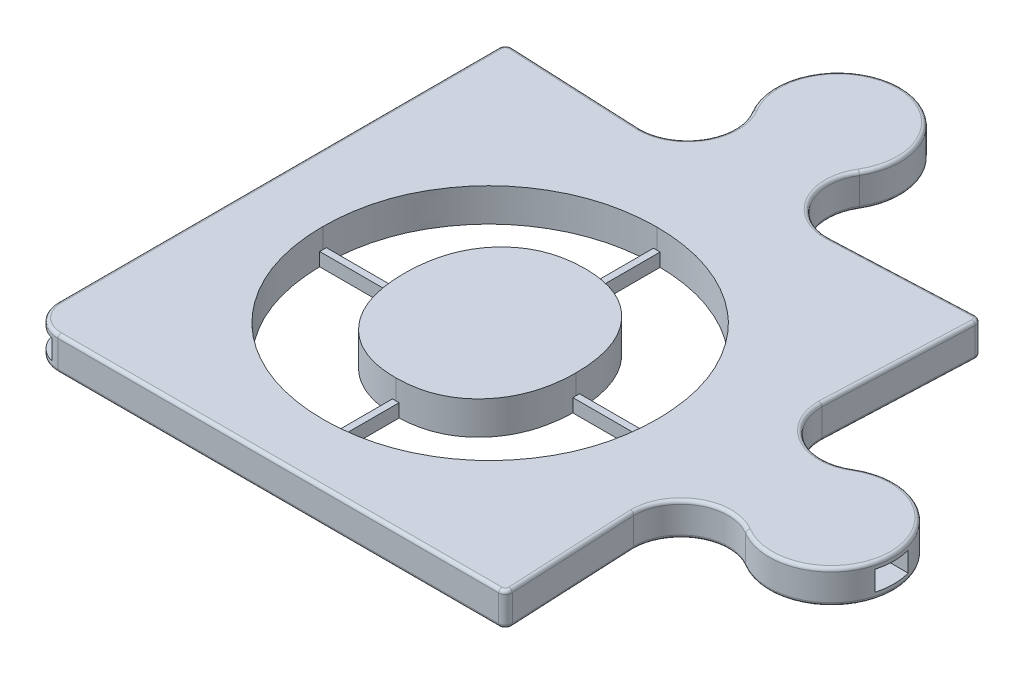
SolidWorks part; units mm, degrees
ref_plane "Front Plane" through (0, 0, 0) normal (0, 0, 1) x (1, 0, 0)
ref_plane "Top Plane" through (0, 0, 0) normal (0, 1, 0) x (1, 0, 0)
ref_plane "Right Plane" through (0, 0, 0) normal (1, 0, 0) x (0, 0, -1)
sketch "Sketch1" plane through (0, 0, 0) normal (0, 1, 0) x (1, 0, 0)
  line L0 (-31, -36) -> (37, -36) construction
  line L1 (-36, 37) -> (-36, -31) construction
  line L2 (-14.1421, 36) -> (-36, 37) construction
  line L3 (37, 37) -> (14.1421, 36) construction
  line L4 (36, 13.1421) -> (37, 37) construction
  line L5 (37, -36) -> (36, -15.1421) construction
  line L6 (-35.4, 36.3719) -> (-35.4, -31)
  line L7 (-36, 36) -> (36, 36) construction
  line L8 (-36, 36) -> (-36, -36) construction
  line L9 (-36, -36) -> (36, -36) construction
  line L10 (36, 36) -> (36, -36) construction
  line L11 (-31, -35.4) -> (36.3705, -35.4)
  line L12 (36.3705, -35.4) -> (35.4, -15.1568)
  line L13 (35.4, 13.155) -> (36.3732, 36.372)
  line L14 (36.3732, 36.372) -> (14.1555, 35.4)
  line L15 (-14.1562, 35.4) -> (-35.4, 36.3719)
  line L16 (-30, -24) -> (30, -24) construction
  line L17 (-30, 29) -> (30, 29) construction
  line L18 (-30, 29) -> (-30, -31) construction
  line L19 (-30, -31) -> (30, -31) construction
  line L20 (30, 29) -> (30, -31) construction
  line L21 (-30, 24) -> (30, 24) construction
  line L22 (-30, 24) -> (-30, -26) construction
  line L23 (-30, -26) -> (30, -26) construction
  line L24 (30, 24) -> (30, -26) construction
  arc A0 (-36, -31) -> (-31, -36) centre (-31, -31) ccw construction
  arc A1 (-14.1421, 36) -> (-8.571, 45.8485) centre (-14.1421, 42.5) ccw construction
  arc A2 (8.571, 45.8485) -> (-8.571, 45.8485) centre (0, 51) ccw construction
  arc A3 (8.571, 45.8485) -> (14.1421, 36) centre (14.1421, 42.5) ccw construction
  arc A4 (36, 13.1421) -> (45.8485, 7.571) centre (42.5, 13.1421) ccw construction
  arc A5 (45.8485, -9.571) -> (45.8485, 7.571) centre (51, -1) ccw construction
  arc A6 (45.8485, -9.571) -> (36, -15.1421) centre (42.5, -15.1421) ccw construction
  arc A7 (-35.4, -31) -> (-31, -35.4) centre (-31, -31) ccw
  arc A8 (46.1576, -9.0567) -> (35.4, -15.1568) centre (42.5, -15.1421) ccw
  arc A9 (46.1576, -9.0567) -> (46.1576, 7.0567) centre (51, -1) ccw
  arc A10 (35.4, 13.155) -> (46.1576, 7.0567) centre (42.5, 13.1421) ccw
  arc A11 (8.0567, 46.1576) -> (14.1555, 35.4) centre (14.1421, 42.5) ccw
  arc A12 (8.0567, 46.1576) -> (-8.0567, 46.1576) centre (0, 51) ccw
  arc A13 (-14.1562, 35.4) -> (-8.0567, 46.1576) centre (-14.1421, 42.5) ccw
  point P32 (36, 0)
  point P34 (0, 36)
  dimension "D5" = 6.5
  dimension "D6" = 10
  dimension "D7" = 6.5
  dimension "D13" = 5
  dimension "D9" = 10
  dimension "D11" = 6.5
  dimension "D12" = 6.5
  dimension "D1" = 72
  dimension "D2" = 1
  dimension "D3" = 1
  dimension "D4" = 15
  dimension "D8" = 1
  dimension "D10" = 35
  dimension "D14" = 15
  dimension "D15" = 36
  dimension "D16" = 1
  dimension "D18" = 60
  dimension "D19" = 60
  dimension "D20" = 5
  dimension "D21" = 6
  dimension "D22" = 5
  dimension "D23" = 50
  dimension "D24" = 2
  dimension "D17" = 0.6
extrude "Boss-Extrude1" add sketch "Sketch1" along normal blind 5
sketch "Sketch6" plane through (0, 0, 0) normal (0, -1, 0) x (1, 0, 0)
  line L0 (-35.4, -36.3719) -> (-35.4, 31) construction
  line L1 (-35.4, 17.9) -> (-27.4, 17.9)
  line L2 (-35.4, 17.9) -> (-35.4, -16.1)
  line L3 (-35.4, -16.1) -> (-27.4, -16.1)
  line L4 (-27.4, 17.9) -> (-27.4, -16.1)
  line L5 (-31, 35.4) -> (36.3705, 35.4) construction
  line L6 (-35.4, 14.65) -> (-30.4, 14.65)
  line L7 (-35.4, 14.65) -> (-35.4, -12.85)
  line L8 (-35.4, -12.85) -> (-30.4, -12.85)
  line L9 (-30.4, 14.65) -> (-30.4, -12.85)
  point P15 (-27.4, 0.9)
  point P16 (-30.4, 0.9)
  line M28 (-35.4, 31) -> (-35.4, -36.3719)
  dimension "D1" = 8
  dimension "D2" = 20.75
  dimension "D3" = 27.5
  dimension "D4" = 5
  dimension "D5" = 34
extrude "Cut-Extrude3" cut sketch "Sketch6" against normal blind 3 from offset 1 contours L6 L9 L8 L3 L4 L1 M28 | L9 L6 L2 L8 region at (-29.8665, 0, 0.9) region at (-32.9, 0, 0.9) offset against normal yes
extrude "Cut-Extrude4" cut sketch "Sketch6<3>" against normal up to next contours L9 L6 L2 L8 region at (-32.9, 0, 0.9)
sketch "Sketch6<3>" plane through (0, 0, 0) normal (0, -1, 0) x (1, 0, 0) same geometry as "Sketch6"
sketch "Sketch8" plane through (0, 0, 0) normal (0, -1, 0) x (1, 0, 0)
  line L1 (-2.5, -51.4) -> (2.5, -51.4)
  line L2 (-2.5, -51.4) -> (-2.5, -60.4)
  line L3 (-2.5, -60.4) -> (2.5, -60.4)
  line L4 (2.5, -51.4) -> (2.5, -60.4)
  line L5 (51.4, 3.5) -> (60.4, 3.5)
  line L6 (51.4, 3.5) -> (51.4, -1.5)
  line L7 (51.4, -1.5) -> (60.4, -1.5)
  line L8 (60.4, 3.5) -> (60.4, -1.5)
  arc A0 (-8.0567, -46.1576) -> (8.0567, -46.1576) centre (0, -51) ccw construction
  arc A1 (46.1576, -7.0567) -> (46.1576, 9.0567) centre (51, 1) ccw construction
  point P4 (0, -60.4)
  point P13 (60.4, 1)
  dimension "D1" = 5
  dimension "D2" = 9
  dimension "D3" = 5
  dimension "D4" = 9
extrude "Cut-Extrude5" cut sketch "Sketch8" against normal blind 3 from offset 1 offset against normal yes
sketch "Sketch9" plane through (0, 0, 0) normal (0, -1, 0) x (1, 0, 0)
  line L0 (-31, 35.4) -> (36.3705, 35.4) construction
  line L1 (-35.4, 14.65) -> (-35.4, 31) construction
  line L2 (-31.7636, 35.3332) -> (-35.4, 31) construction
  line L3 (-33.2571, 29.735) -> (-30.0429, 33.565) construction
  line L4 (-30.0429, 33.565) -> (-33.2571, 29.735) construction
  line L5 (-30.0429, 33.565) -> (-32.7119, 35.8048)
  line L6 (-33.2571, 29.735) -> (-35.926, 31.9747)
  line L7 (-32.7119, 35.8048) -> (-35.926, 31.9747)
  circle A0 centre (-31.65, 31.65) radius 2.5
  arc A1 (-31, 35.4) -> (-35.4, 31) centre (-31, 31) ccw construction
  arc M41 (-31, 35.4) -> (-35.4, 31) centre (-31, 31) ccw
  dimension "D1" = 5
  dimension "D3" = 3.75
  dimension "D4" = 5.6569
  dimension "D2" = 3.75
extrude "Cut-Extrude6" cut sketch "Sketch9" against normal blind 3 from offset 1 contours A0 L5 L6 M41 | A0 L5 region at (-33.6239, 0, 33.3064) region at (-31.65, 0, 31.65) offset against normal yes
sketch "Sketch11" plane through (-35.4, 0, 0) normal (-1, 0, 0) x (0, 0, 1)
  line L0 (-13.155, 0) -> (-36.372, 0) construction
  line L1 (-25.1, 3) -> (-19.1, 3)
  line L2 (-25.1, 3) -> (-25.1, 1.5)
  line L3 (-25.1, 1.5) -> (-19.1, 1.5)
  line L4 (-19.1, 3) -> (-19.1, 1.5)
  line L5 (-16.1, 4) -> (-16.1, 1) construction
  line L6 (35.4, 0) -> (15.1568, 0) construction
  line L7 (20.9, 3) -> (26.9, 3)
  line L8 (20.9, 3) -> (20.9, 1.5)
  line L9 (20.9, 1.5) -> (26.9, 1.5)
  line L10 (26.9, 3) -> (26.9, 1.5)
  line L12 (17.9, 4) -> (17.9, 1) construction
  dimension "D1" = 3
  dimension "D2" = 1.5
  dimension "D3" = 3
  dimension "D4" = 6
  dimension "D5" = 3
  dimension "D6" = 1.5
  dimension "D7" = 6
  dimension "D8" = 3
fillet "Fillet1" radius 0.5 17 edges at (-35.4, 0, 22.825) (-34.1113, 0, 34.1113) (2.6853, 0, 35.4) (35.8853, 0, 25.2784) (38.9978, 0, 8.966) (60.4, 0, 1) (38.9986, 0, -6.9655) (35.8866, 0, -24.7635) (25.2643, 0, -35.886) (7.9657, 0, -38.9984) (0, 0, -60.4) (-7.9658, 0, -38.9981) (-24.7781, 0, -35.886) (-35.4, 0, -24.611) (-32.9, 0, -12.85) (-30.4, 0, 0.9) (-32.9, 0, 14.65)
fillet "Fillet2" radius 0.5 13 edges at (-7.9658, 5, -38.9981) (0, 5, -60.4) (7.9657, 5, -38.9984) (25.2643, 5, -35.886) (35.8866, 5, -24.7635) (38.9986, 5, -6.9655) (60.4, 5, 1) (38.9978, 5, 8.966) (35.8853, 5, 25.2784) (2.6853, 5, 35.4) (-34.1113, 5, 34.1113) (-35.4, 5, -2.686) (-24.7781, 5, -35.886)
fillet "Fillet3" radius 1 9 edges at (36.2202, 0.1464, -36.2187) (36.2202, 4.8536, -36.2187) (36.3732, 2.5, -36.372) (-35.2536, 0.1464, -36.2186) (-35.2536, 4.8536, -36.2186) (36.2169, 0.1464, 35.2536) (36.2169, 4.8536, 35.2536) (36.3705, 2.5, 35.4) (-35.4, 2.5, -36.3719)
extrude "Cut-Extrude9" cut sketch "Sketch11" against normal blind 3
chamfer "Chamfer1" distance 1 angle 50 2 edges at (-35.4, 1.5, 23.9) (-35.4, 1.5, -22.1) first distance on face at (-35.4, 2.25, -22.1)
sketch "Sketch12" plane through (0, 5, 0) normal (0, 1, 0) x (1, 0, 0)
  text T0 "O" font "Poppins" height 49
extrude "Cut-Extrude10" cut sketch "Sketch12" against normal through all
sketch "Sketch13" plane through (0, 5, 0) normal (0, 1, 0) x (1, 0, 0)
  line L0 (0, 24) -> (0.0303, -26.4847) construction
  line L1 (-30, 24) -> (30, 24) construction
  line L2 (-25.1665, -1.3586) -> (25.0958, -1.3586) construction
  line L4 (-25.1589, -0.8614) -> (-12.9392, -0.8614)
  line L5 (-25.1589, -0.8614) -> (-25.1589, -1.8614)
  line L6 (-25.1589, -1.8614) -> (-12.9392, -1.8614)
  line L7 (-12.9392, -0.8614) -> (-12.9392, -1.8614)
  line L8 (-0.4686, 12.8686) -> (0.5314, 12.8686)
  line L9 (-0.4686, 12.8686) -> (-0.4686, 23.6878)
  line L10 (-0.4686, 23.6878) -> (0.5314, 23.6878)
  line L11 (0.5314, 12.8686) -> (0.5314, 23.6878)
  line L12 (0.5303, -15.5856) -> (-0.4697, -15.5856)
  line L13 (0.5303, -15.5856) -> (0.5303, -26.4758)
  line L14 (0.5303, -26.4758) -> (-0.4697, -26.4758)
  line L15 (-0.4697, -15.5856) -> (-0.4697, -26.4758)
  line L16 (12.9391, -1.8523) -> (25.0882, -1.8523)
  line L17 (12.9391, -1.8523) -> (12.9391, -0.8523)
  line L18 (12.9391, -0.8523) -> (25.0882, -0.8523)
  line L19 (25.0882, -1.8523) -> (25.0882, -0.8523)
  spline S0 degree 3 poles (-25.1665, -1.3586) (-25.158, -0.7657) (-25.1413, 0.4055) (-24.9715, 2.1354) (-24.7121, 3.8229) (-24.3394, 5.4626) (-23.8605, 7.0572) (-23.2882, 8.6058) (-22.5965, 10.1065) (-21.7999, 11.5554) (-20.9138, 12.9437) (-19.9533, 14.2599) (-18.9184, 15.4988) (-17.8112, 16.6553) (-16.6304, 17.7394) (-15.366, 18.7289) (-14.0455, 19.6707) (-12.6382, 20.4966) (-11.1928, 21.2616) (-9.6889, 21.9035) (-8.1562, 22.4608) (-6.5888, 22.9194) (-4.9838, 23.2583) (-3.3459, 23.5132) (-1.6693, 23.668) (-0.5389, 23.6872) (0.0303, 23.6968) knots 0 0 0 0 0.04484 0.08858 0.131371 0.173938 0.215675 0.257256 0.298736 0.340565 0.382247 0.423253 0.463751 0.50428 0.544298 0.584907 0.625674 0.666905 0.708254 0.749318 0.790485 0.831589 0.872748 0.914494 0.956941 1 1 1 1 construction
  spline S1 degree 3 poles (-12.9468, -1.3586) (-12.9398, -1.8877) (-12.9261, -2.9186) (-12.7421, -4.4232) (-12.4797, -5.8477) (-12.0907, -7.1924) (-11.6004, -8.4567) (-10.9892, -9.6372) (-10.2689, -10.7342) (-9.4419, -11.7421) (-8.5249, -12.6492) (-7.5321, -13.4479) (-6.4478, -14.1052) (-5.2974, -14.6507) (-4.0725, -15.08) (-2.7722, -15.3798) (-1.3956, -15.5652) (-0.4517, -15.587) (0.0303, -15.5981) knots 0 0 0 0 0.072957 0.142149 0.208827 0.272625 0.334984 0.395642 0.455672 0.515736 0.575181 0.633355 0.691107 0.749695 0.808745 0.869807 0.933524 1 1 1 1 construction
  spline S2 degree 3 poles (0.0303, 12.8809) (-0.4518, 12.8701) (-1.3959, 12.849) (-2.7705, 12.6588) (-4.0746, 12.3771) (-5.2939, 11.9393) (-6.4542, 11.4131) (-7.5255, 10.7376) (-8.5257, 9.9541) (-9.4411, 9.0548) (-10.2718, 8.0564) (-10.9892, 6.9601) (-11.5978, 5.7823) (-12.0949, 4.5203) (-12.4789, 3.1705) (-12.7432, 1.733) (-12.9254, 0.2147) (-12.9396, -0.8262) (-12.9468, -1.3586) knots 0 0 0 0 0.066421 0.130085 0.190992 0.249994 0.308336 0.366284 0.424122 0.483193 0.542849 0.60283 0.663437 0.725312 0.789504 0.856583 0.92664 1 1 1 1 construction
  spline S3 degree 3 poles (0.0303, 23.6968) (0.5995, 23.6872) (1.7299, 23.6681) (3.4097, 23.5123) (5.0513, 23.2594) (6.6595, 22.9193) (8.2269, 22.4609) (9.7596, 21.9035) (11.2634, 21.2615) (12.7092, 20.497) (14.1152, 19.6695) (15.4361, 18.7364) (16.6812, 17.728) (17.8727, 16.6664) (18.957, 15.4935) (19.9852, 14.2634) (20.9232, 12.9425) (21.791, 11.5553) (22.5645, 10.1035) (23.2495, 8.6061) (23.8069, 7.0549) (24.292, 5.4642) (24.6514, 3.8223) (24.8982, 2.1345) (25.0713, 0.4055) (25.0876, -0.7657) (25.0958, -1.3586) knots 0 0 0 0 0.043126 0.085641 0.127704 0.168928 0.210097 0.251329 0.292458 0.333872 0.375167 0.415999 0.456273 0.496543 0.536784 0.577183 0.617954 0.65943 0.701082 0.742521 0.78408 0.825882 0.868461 0.911281 0.955089 1 1 1 1 construction
  spline S4 degree 3 poles (0.0303, -15.5981) (0.509, -15.5872) (1.443, -15.566) (2.8056, -15.3781) (4.0981, -15.0816) (5.3121, -14.6386) (6.4653, -14.0998) (7.5269, -13.4108) (8.5292, -12.6207) (9.4417, -11.7007) (10.2661, -10.685) (10.9899, -9.587) (11.5977, -8.4085) (12.0931, -7.1496) (12.4779, -5.8102) (12.7425, -4.393) (12.9256, -2.9018) (12.9396, -1.881) (12.9468, -1.3586) knots 0 0 0 0 0.06625 0.129273 0.190101 0.24952 0.307898 0.365957 0.424341 0.484329 0.544971 0.605218 0.666094 0.728244 0.792272 0.858734 0.927712 1 1 1 1 construction
  spline S5 degree 3 poles (0.0303, -26.4847) (-0.539, -26.4752) (-1.6694, -26.4562) (-3.3456, -26.2999) (-4.9856, -26.0506) (-6.5855, -25.6907) (-8.1583, -25.2528) (-9.6886, -24.6902) (-11.1929, -24.0499) (-12.6381, -23.2844) (-14.0456, -22.4588) (-15.3655, -21.5162) (-16.6341, -20.528) (-17.8072, -19.4323) (-18.9226, -18.2769) (-19.9495, -17.0278) (-20.9173, -15.7104) (-21.7993, -14.3124) (-22.5971, -12.8542) (-23.2854, -11.3455) (-23.8652, -9.7893) (-24.3339, -8.1884) (-24.7154, -6.5442) (-24.9702, -4.8557) (-25.1415, -3.1227) (-25.1581, -1.9515) (-25.1665, -1.3586) knots 0 0 0 0 0.042993 0.085377 0.127059 0.168211 0.209183 0.250287 0.29129 0.332576 0.373744 0.41445 0.454997 0.495127 0.535594 0.576227 0.617171 0.659005 0.700994 0.742642 0.78416 0.826321 0.868577 0.911554 0.955227 1 1 1 1 construction
  spline S6 degree 3 poles (25.0958, -1.3586) (25.0874, -1.9515) (25.0706, -3.1227) (24.9004, -4.8559) (24.6413, -6.5426) (24.2764, -8.1898) (23.8043, -9.7894) (23.2232, -11.3432) (22.5475, -12.8542) (21.7589, -14.3121) (20.8871, -15.7101) (19.9295, -17.0277) (18.9121, -18.276) (17.8078, -19.4363) (16.6347, -20.5204) (15.3847, -21.5234) (14.0666, -22.4548) (12.669, -23.285) (11.2333, -24.0497) (9.7392, -24.6901) (8.2161, -25.2546) (6.646, -25.6904) (5.0462, -26.0506) (3.4062, -26.2999) (1.73, -26.4562) (0.5995, -26.4752) (0.0303, -26.4847) knots 0 0 0 0 0.044872 0.088642 0.131716 0.174009 0.216264 0.257874 0.29951 0.341471 0.383262 0.424147 0.464707 0.505089 0.545308 0.585547 0.626343 0.667384 0.708536 0.749396 0.790352 0.831415 0.872658 0.914433 0.956911 1 1 1 1 construction
  spline S7 degree 3 poles (12.9468, -1.3586) (12.9398, -0.8295) (12.926, 0.2014) (12.7423, 1.706) (12.4793, 3.1303) (12.093, 4.4727) (11.5979, 5.7318) (10.9895, 6.9099) (10.2689, 8.0069) (9.4417, 9.0145) (8.5256, 9.9229) (7.5305, 10.716) (6.4617, 11.3899) (5.3148, 11.935) (4.0957, 12.3611) (2.8059, 12.6618) (1.4429, 12.8485) (0.5089, 12.8699) (0.0303, 12.8809) knots 0 0 0 0 0.073165 0.142553 0.209421 0.273401 0.335504 0.396334 0.456535 0.516771 0.576385 0.634725 0.692491 0.750825 0.810043 0.870825 0.9338 1 1 1 1 construction
  dimension "D1" = 1
  dimension "D2" = 1
  dimension "D3" = 1
  dimension "D4" = 1
extrude "Boss-Extrude2" add sketch "Sketch13" along normal blind 2 from surface starting at face at (0.0151, 0, 1.3586)
